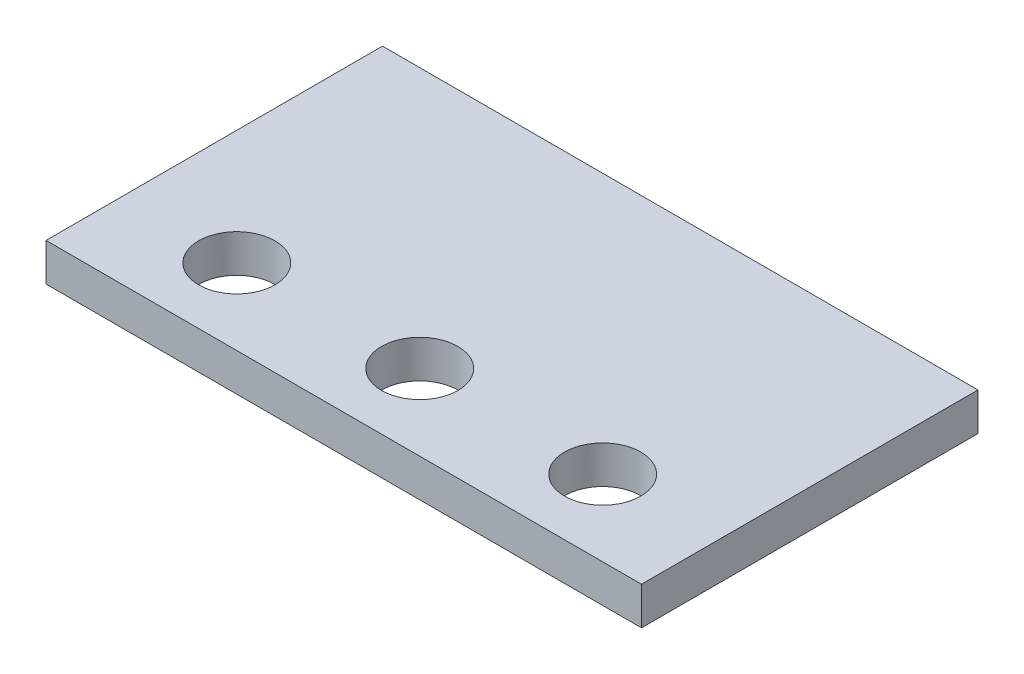
SolidWorks part; units mm, degrees
ref_plane "Alzado" through (0, 0, 0) normal (0, 0, 1) x (1, 0, 0)
ref_plane "Planta" through (0, 0, 0) normal (0, 1, 0) x (1, 0, 0)
ref_plane "Vista lateral" through (0, 0, 0) normal (1, 0, 0) x (0, 0, -1)
ref_plane "Plano2" through (0, 0, 360) normal (0, 0, -1) x (-1, 0, 0)
sketch "Croquis1" plane through (0, 0, 360) normal (0, 0, -1) x (-1, 0, 0)
  line L0 (-149.7459, -167.1656) -> (165.2541, -167.1656)
  line L1 (-177.2459, -167.1656) -> (192.7541, -167.1656) construction
  line L2 (7.7541, -167.1656) -> (7.7541, -33.1806) construction
  line L4 (-149.7459, -167.1656) -> (165.2541, -167.1656)
  line L5 (-149.7459, -167.1656) -> (-149.7459, -147.1656)
  line L6 (-149.7459, -147.1656) -> (165.2541, -147.1656)
  line L7 (165.2541, -167.1656) -> (165.2541, -147.1656)
  point P5 (7.7541, -167.1656)
  dimension "D1" = 315
  dimension "D2" = 20
extrude "Saliente-Extruir1" add sketch "Croquis1" along normal blind 178 contours L0 L2 L6 L5 | L2 L4 L7 L6 region at (70.9959, -157.1656, 360) region at (-86.5041, -157.1656, 360)
sketch "Croquis2" plane through (0, -167.1656, 0) normal (0, -1, 0) x (1, 0, 0)
  line L0 (-7.7541, 360) -> (-7.7541, 340) construction
  line L2 (149.7459, 360) -> (-165.2541, 360) construction
  circle A0 centre (-104.5195, 319.8097) radius 20.1903
  circle A1 centre (-7.7541, 319.8097) radius 20.1903
  circle A2 centre (89.0113, 319.8097) radius 20.1903
  point P7 (0, 0)
  point P11 (-7.7541, 318.9574)
  point P12 (0, 0)
  point P13 (-102.0361, 319.8097)
  point P14 (-92.5166, 320.2236)
  point P15 (-93.3444, 316.0847)
  point P16 (-104.5195, 319.8097)
  dimension "D1" = 20
  dimension "D2" = 3
extrude "Cortar-Extruir1" cut sketch "Croquis2" against normal up to next contours A2 | A1 | A0
